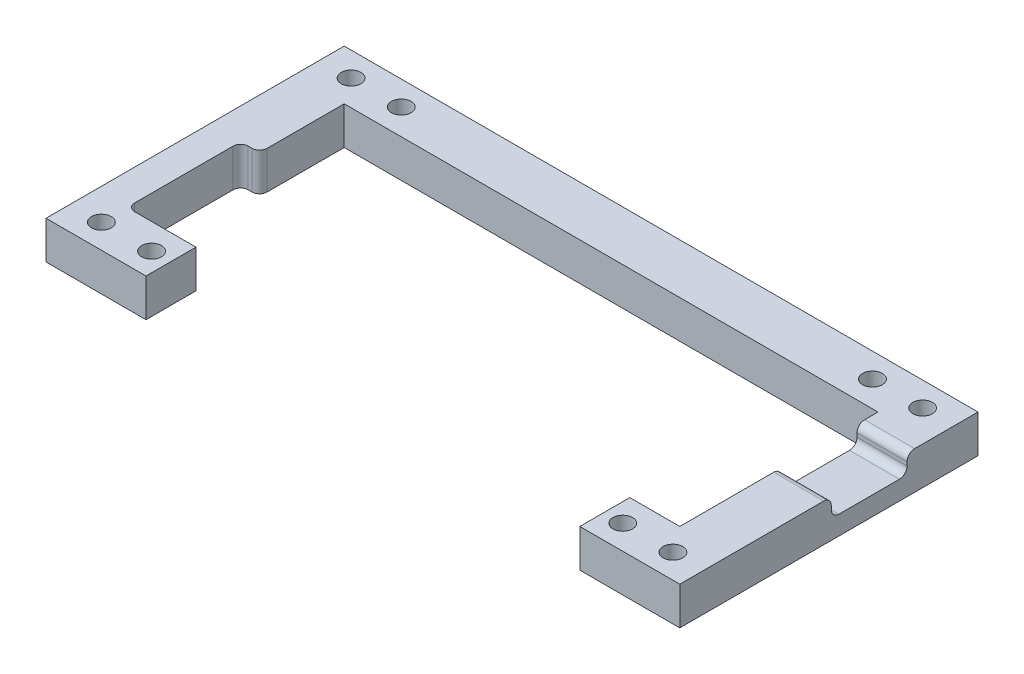
SolidWorks part; units mm, degrees
ref_plane "Front Plane" through (0, 0, 0) normal (0, 0, 1) x (1, 0, 0)
ref_plane "Top Plane" through (0, 0, 0) normal (0, 1, 0) x (1, 0, 0)
ref_plane "Right Plane" through (0, 0, 0) normal (1, 0, 0) x (0, 0, -1)
sketch "Sketch1" plane through (0, 0, 0) normal (0, 1, 0) x (1, 0, 0)
  line L0 (181.4198, 36.9979) -> (75.1552, 36.9979) construction
  line L1 (75.1552, 11.9979) -> (83.5372, 11.9979)
  line L2 (75.1552, 11.9979) -> (75.1552, 61.9979)
  line L3 (75.1552, 61.9979) -> (83.5372, 61.9979)
  line L4 (83.5372, 11.9979) -> (83.5372, 61.9979)
  line L5 (83.5372, 61.9979) -> (91.9192, 61.9979)
  line L6 (83.5372, 61.9979) -> (83.5372, 53.6159)
  line L7 (83.5372, 53.6159) -> (91.9192, 53.6159)
  line L8 (167.7876, 16.0648) -> (186.7138, 16.0648) construction
  line L9 (83.5372, 11.9979) -> (91.9192, 11.9979)
  line L10 (83.5372, 11.9979) -> (83.5372, 20.3799)
  line L11 (83.5372, 20.3799) -> (91.9192, 20.3799)
  line L12 (91.9192, 11.9979) -> (91.9192, 20.3799)
  line L13 (75.1552, 61.9979) -> (181.4198, 61.9979)
  line L17 (181.4198, 61.9979) -> (173.0378, 61.9979)
  line L18 (181.4198, 61.9979) -> (181.4198, 11.9979)
  line L19 (181.4198, 11.9979) -> (173.0378, 11.9979)
  line L20 (173.0378, 61.9979) -> (173.0378, 11.9979)
  line L21 (173.0378, 61.9979) -> (164.6558, 61.9979)
  line L22 (173.0378, 61.9979) -> (173.0378, 53.6159)
  line L23 (173.0378, 53.6159) -> (164.6558, 53.6159)
  line L25 (173.0378, 11.9979) -> (164.6558, 11.9979)
  line L26 (173.0378, 11.9979) -> (173.0378, 20.3799)
  line L27 (173.0378, 20.3799) -> (164.6558, 20.3799)
  line L28 (164.6558, 11.9979) -> (164.6558, 20.3799)
  line L29 (128.2875, 61.9979) -> (128.2875, -9.1774) construction
  line L30 (164.6558, 53.6159) -> (91.9192, 53.6159)
  circle A0 centre (167.7876, 57.931) radius 1.651
  circle A1 centre (167.7876, 16.0648) radius 1.651
  circle A2 centre (88.7875, 16.0648) radius 1.651
  circle A3 centre (88.7875, 57.931) radius 1.651
  circle A4 centre (176.2028, 16.0648) radius 1.651
  circle A5 centre (80.3722, 16.0648) radius 1.651
  circle A6 centre (80.3722, 57.931) radius 1.651
  circle A7 centre (176.2028, 57.931) radius 1.651
  point P32 (91.9192, 16.1889)
  point P34 (88.7875, 57.931)
  point P35 (88.7875, 16.0648)
  dimension "D15" = 3.302
  dimension "D16" = 3.1342
  dimension "D6" = 79.0001
  dimension "D18" = 3.302
  dimension "D2" = 47.9153
  dimension "D1" = 8.382
  dimension "D3" = 50
  dimension "D4" = 8.382
  dimension "D5" = 50
  dimension "D7" = 8.382
  dimension "D8" = 8.382
  dimension "D9" = 8.382
  dimension "D10" = 8.382
  dimension "D11" = 8.382
  dimension "D12" = 8.382
  dimension "D13" = 8.382
  dimension "D14" = 8.382
  dimension "D17" = 3.1317
extrude "Boss-Extrude1" add sketch "Sketch1" along normal blind 6.35 contours L1 L4 L3 L2 | L13 L3 L5 | L13 L20 L19 L18 | L13 L23 L20 | L28 L25 L20 L27 | L9 L12 L11 L4 | L5 L4 L7 | L1 L4 L2 | L20 L19 L18 region at (79.3025, 0, -36.9979) region at (83.6557, 0, -16.1889) region at (128.2875, 0, -57.804) region at (177.2725, 0, -36.9979) region at (172.9193, 0, -16.1889)
sketch "Sketch2" plane through (181.4198, 0, 0) normal (1, 0, 0) x (0, 0, -1)
  line L0 (61.9979, 6.35) -> (11.9979, 6.35) construction
  line L1 (37.3979, 6.35) -> (50.0979, 6.35)
  line L2 (37.3979, 6.35) -> (37.3979, 3.175)
  line L3 (37.3979, 3.175) -> (50.0979, 3.175)
  line L4 (50.0979, 6.35) -> (50.0979, 3.175)
  line L5 (11.9979, 6.35) -> (11.9979, 0) construction
  dimension "D1" = 25.4
  dimension "D2" = 12.7
  dimension "D3" = 3.175
extrude "Cut-Extrude7" cut sketch "Sketch2" against normal blind 8.89 contours L2 L3 L4 L1
fillet "Fillet2" radius 1.27 4 edges at (177.2288, 3.175, -37.3979) (177.2288, 6.35, -37.3979) (177.2288, 6.35, -50.0979) (177.2288, 3.175, -50.0979)
sketch "Sketch4" plane through (0, 6.35, 0) normal (0, 1, 0) x (1, 0, 0)
  line L1 (83.5372, 20.3799) -> (80.3622, 20.3799)
  line L2 (83.5372, 20.3799) -> (83.5372, 39.4299)
  line L3 (83.5372, 39.4299) -> (80.3622, 39.4299)
  line L4 (80.3622, 20.3799) -> (80.3622, 39.4299)
  dimension "D1" = 3.175
  dimension "D2" = 19.05
extrude "Cut-Extrude8" cut sketch "Sketch4" against normal through all
fillet "Fillet3" radius 1.27 3 edges at (80.3622, 3.175, -20.3799) (80.3622, 3.175, -39.4299) (83.5372, 3.175, -39.4299)
sketch "Sketch5" plane through (0, 0, 0) normal (0, -1, 0) x (1, 0, 0)
  circle A0 centre (88.7875, -16.0648) radius 2.8575
  circle A1 centre (88.7875, -57.931) radius 3.175
  circle A2 centre (167.7876, -57.931) radius 3.175
  circle A3 centre (167.7876, -16.0648) radius 2.8575
  dimension "D1" = 5.715
  dimension "D2" = 6.35
  dimension "D3" = 5.715
  dimension "D4" = 6.35
extrude "Cut-Extrude9" cut sketch "Sketch5" against normal blind 2.54
